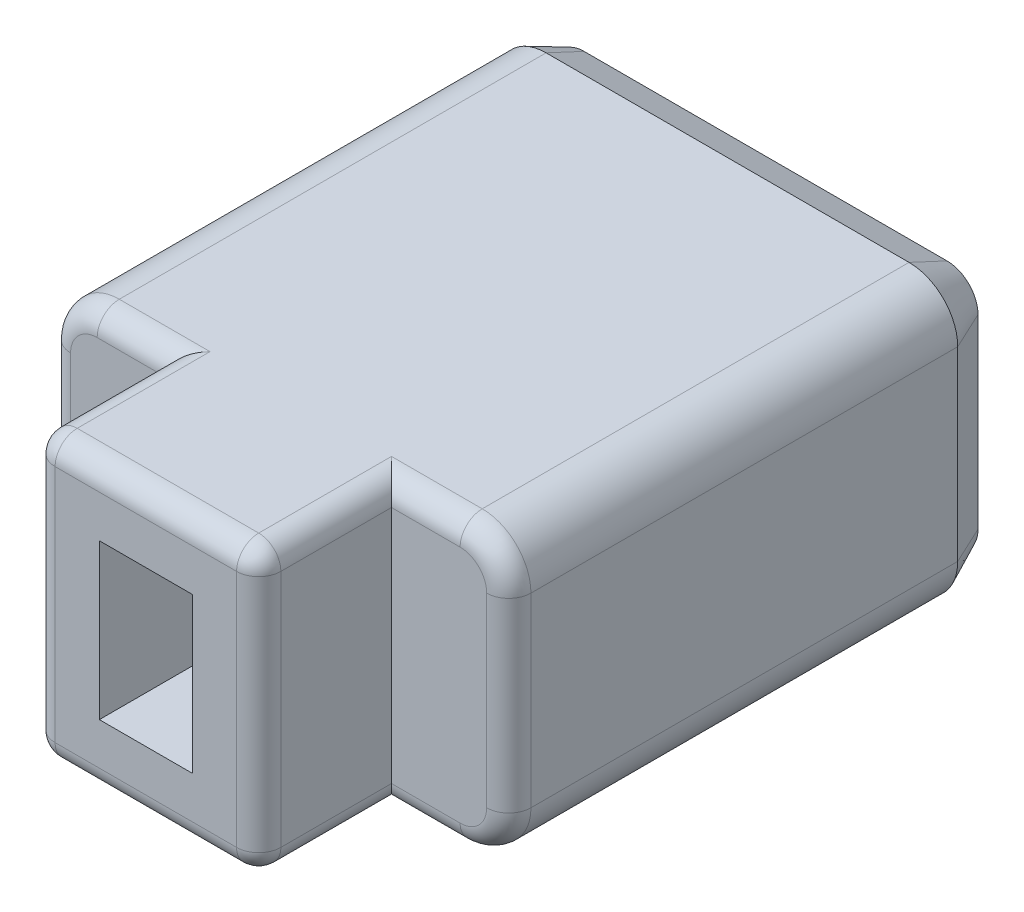
SolidWorks part; units mm, degrees
ref_plane "Plan de face" through (0, 0, 0) normal (0, 0, 1) x (1, 0, 0)
ref_plane "Plan de dessus" through (0, 0, 0) normal (0, 1, 0) x (1, 0, 0)
ref_plane "Plan de droite" through (0, 0, 0) normal (1, 0, 0) x (0, 0, -1)
sketch "Esquisse2" plane through (0, 0, 0) normal (0, 0, 1) x (1, 0, 0)
  line L1 (1.1, 0) -> (9.3, 0)
  line L2 (0, 1.1) -> (0, 5.3)
  line L3 (1.1, 6.4) -> (9.3, 6.4)
  line L4 (10.4, 1.1) -> (10.4, 5.3)
  arc A0 (9.3, 6.4) -> (10.4, 5.3) centre (9.3, 5.3) cw
  arc A1 (9.3, 0) -> (10.4, 1.1) centre (9.3, 1.1) ccw
  arc A2 (1.1, 0) -> (0, 1.1) centre (1.1, 1.1) cw
  arc A3 (0, 5.3) -> (1.1, 6.4) centre (1.1, 5.3) cw
  point P7 (10.4, 6.4)
  point P12 (0, 0)
  point P15 (0, 6.4)
  dimension "D3" = 1.1
  dimension "D1" = 10.4
  dimension "D2" = 6.4
extrude "Boss.-Extru.1" add sketch "Esquisse2" along normal blind 14
sketch "Esquisse3" plane through (0, 0, 14) normal (0, 0, 1) x (1, 0, 0)
  line L0 (0, 5.3) -> (0, 1.1) construction
  line L1 (4.15, 4.95) -> (6.25, 4.95)
  line L2 (4.15, 4.95) -> (4.15, 1.45)
  line L3 (4.15, 1.45) -> (6.25, 1.45)
  line L4 (6.25, 4.95) -> (6.25, 1.45)
  line L5 (10.4, 1.1) -> (10.4, 5.3) construction
  line L6 (9.3, 6.4) -> (1.1, 6.4) construction
  line L7 (1.1, 0) -> (9.3, 0) construction
  dimension "D1" = 2.1
  dimension "D2" = 3.5
  dimension "D3" = 4.15
  dimension "D4" = 4.15
  dimension "D5" = 1.45
  dimension "D6" = 1.45
extrude "Enlèv. mat.-Extru.1" cut sketch "Esquisse3" against normal blind 3
sketch "Esquisse4" plane through (0, 0, 14) normal (0, 0, 1) x (1, 0, 0)
  line L0 (2.65, 6.4) -> (2.65, 0)
  line L1 (9.3, 6.4) -> (1.1, 6.4) construction
  line L2 (1.1, 0) -> (9.3, 0) construction
  line L3 (2.65, 0) -> (7.75, 0)
  line L4 (7.75, 0) -> (7.75, 6.4)
  line L5 (7.75, 6.4) -> (2.65, 6.4)
  line L6 (4.15, 4.95) -> (4.15, 1.45) construction
  line L7 (6.25, 1.45) -> (6.25, 4.95) construction
  dimension "D1" = 1.5
  dimension "D2" = 1.5
extrude "Enlèv. mat.-Extru.2" cut sketch "Esquisse4" against normal blind 3 flip side to cut
fillet "Congé1" radius 0.5 18 edges at (8.525, 0, 11) (10.0778, 0.3222, 11) (10.4, 3.2, 11) (10.0778, 6.0778, 11) (1.875, 6.4, 11) (0.3222, 6.0778, 11) (1.875, 0, 11) (0.3222, 0.3222, 11) (7.75, 6.4, 12.5) (2.65, 6.4, 12.5) (7.75, 0, 12.5) (2.65, 0, 12.5) (2.65, 3.2, 14) (5.2, 6.4, 14) (7.75, 3.2, 14) (5.2, 0, 14) (8.525, 6.4, 11) (0, 3.2, 11)
chamfer "Chanfrein1" distance 0.4 angle 65 8 edges at (5.2, 0, 0) (10.0778, 0.3222, 0) (0.3222, 0.3222, 0) (10.4, 3.2, 0) (0, 3.2, 0) (10.0778, 6.0778, 0) (0.3222, 6.0778, 0) (5.2, 6.4, 0) first distance on face at (5.2, 3.2, 0)
sketch "Esquisse5" plane through (0, 0, 0) normal (0, 0, -1) x (-1, 0, 0)
  line L0 (-0.4, 5.3) -> (-10, 5.3) construction
  arc A0 (-9.3, 6) -> (-10, 5.3) centre (-9.3, 5.3) ccw construction
  text T0 "3" font "Century Gothic" height 4
extrude "Enlèv. mat.-Extru.3" cut sketch "Esquisse5" against normal blind 0.3
extrude "Boss.-Extru.2" add sketch "Esquisse5<2>" along normal blind 0.3 separate body
sketch "Esquisse5<2>" plane through (0, 0, 0) normal (0, 0, -1) x (-1, 0, 0) same geometry as "Esquisse5"
